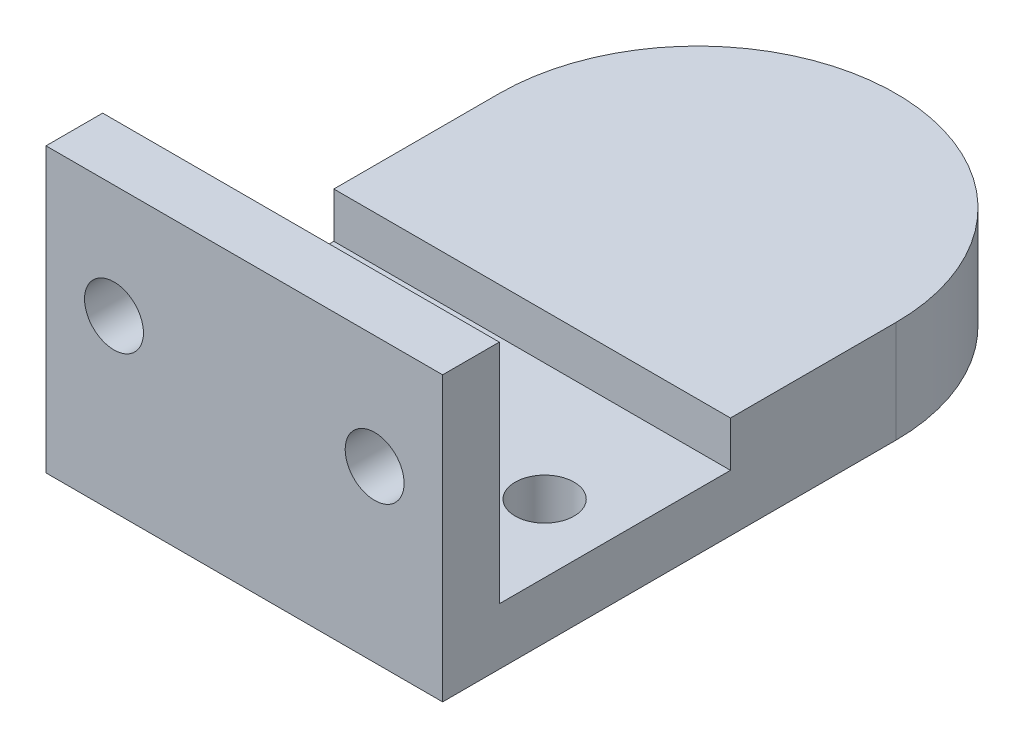
SolidWorks part; units mm, degrees
material "PET"
ref_plane "Front Plane" through (0, 0, 0) normal (0, 0, 1) x (1, 0, 0)
ref_plane "Top Plane" through (0, 0, 0) normal (0, 1, 0) x (1, 0, 0)
ref_plane "Right Plane" through (0, 0, 0) normal (1, 0, 0) x (0, 0, -1)
sketch "Sketch1" plane through (0, 0, 0) normal (0, 1, 0) x (1, 0, 0)
  line L5 (-17.5, 0) -> (-17.5, -15)
  line L6 (17.5, 0) -> (17.5, -15)
  line L9 (-17.5, -15) -> (17.5, -15)
  circle A0 centre (0, 0) radius 11.1
  arc A1 (17.5, 0) -> (-17.5, 0) centre (0, 0) ccw
  dimension "D1" = 22.2
  dimension "D2" = 35
  dimension "D3" = 15
extrude "Boss-Extrude1" add sketch "Sketch1" along normal blind 7
sketch "Sketch4" plane through (0, 0, 0) normal (0, 1, 0) x (1, 0, 0)
  line L0 (-17.5, -15) -> (17.5, -15) construction
  line L1 (-17.5, -15) -> (17.5, -15)
  line L2 (-17.5, -15) -> (-17.5, -35)
  line L3 (-17.5, -35) -> (17.5, -35)
  line L4 (17.5, -15) -> (17.5, -35)
  line L5 (-17.5, 0) -> (-17.5, -15) construction
  point P6 (0, -15)
  dimension "D1" = 20
extrude "Boss-Extrude3" add sketch "Sketch4" along normal blind 5
sketch "Sketch5" plane through (0, 7, 0) normal (0, 1, 0) x (1, 0, 0)
  line L0 (-17.5, -35) -> (17.5, -35) construction
  line L1 (-17.5, 0) -> (-17.5, -15) construction
  line L2 (17.5, -15) -> (17.5, 0) construction
  circle A0 centre (-11.5, -25) radius 2.6
  circle A1 centre (11.5, -25) radius 2.6
  dimension "D1" = 5.2
  dimension "D2" = 5.2
  dimension "D3" = 10
  dimension "D4" = 10
  dimension "D5" = 6
  dimension "D6" = 6
extrude "Cut-Extrude1" cut sketch "Sketch5" against normal through all
sketch "Sketch8" plane through (0, 7, 0) normal (0, 1, 0) x (1, 0, 0)
  line L0 (-17.5, -35) -> (17.5, -35) construction
  line L5 (-17.5, 0) -> (-17.5, -15)
  line L6 (17.5, 0) -> (17.5, -15)
  line L9 (-17.5, -15) -> (17.5, -15)
  arc A1 (17.5, 0) -> (-17.5, 0) centre (0, 0) ccw
  dimension "D1" = 20
  dimension "D2" = 35
extrude "Boss-Extrude4" add sketch "Sketch8" along normal blind 2
sketch "Sketch9" plane through (0, 0, 0) normal (0, -1, 0) x (1, 0, 0)
  line L0 (17.5, 35) -> (17.5, 0) construction
  line L1 (-17.5, 35) -> (17.5, 35)
  line L2 (-17.5, 35) -> (-17.5, 40)
  line L3 (-17.5, 40) -> (17.5, 40)
  line L4 (17.5, 35) -> (17.5, 40)
  dimension "D1" = 5
extrude "Boss-Extrude5" add sketch "Sketch9" against normal blind 25
sketch "Sketch10" plane through (0, 0, 35) normal (0, 0, -1) x (-1, 0, 0)
  line L0 (-17.5, 25) -> (-17.5, 5) construction
  line L1 (17.5, 25) -> (17.5, 5) construction
  line L2 (17.5, 25) -> (-17.5, 25) construction
  circle A0 centre (-11.5, 15) radius 2.6
  circle A1 centre (11.5, 15) radius 2.6
  dimension "D1" = 5.2
  dimension "D2" = 5.2
  dimension "D3" = 6
  dimension "D4" = 6
  dimension "D5" = 10
  dimension "D6" = 10
extrude "Cut-Extrude2" cut sketch "Sketch10" against normal blind 25
sketch "Sketch11" plane through (0, 9, 0) normal (0, 1, 0) x (1, 0, 0)
  line L0 (17.5, -15) -> (17.5, 0) construction
  line L1 (-17.5, -15) -> (17.5, -15)
  line L2 (-17.5, -15) -> (-17.5, -14.6)
  line L3 (-17.5, -14.6) -> (17.5, -14.6)
  line L4 (17.5, -15) -> (17.5, -14.6)
  dimension "D1" = 0.4
extrude "Cut-Extrude3" cut sketch "Sketch11" against normal up to surface (4 mm away) up to face at (11.5, 5, 27.6)
equation "\"tolerance\"= 0.2"
equation "\"D1@Sketch1\"=\"tolerance\"+22"
equation "\"D1@Sketch5\"=\"tolerance\"+5"
equation "\"D2@Sketch5\"=\"tolerance\"+5"
equation "\"D1@Sketch10\"=\"tolerance\"+5"
equation "\"D2@Sketch10\"=\"tolerance\"+5"
equation "\"D1@Sketch11\"=2 * \"tolerance\""
